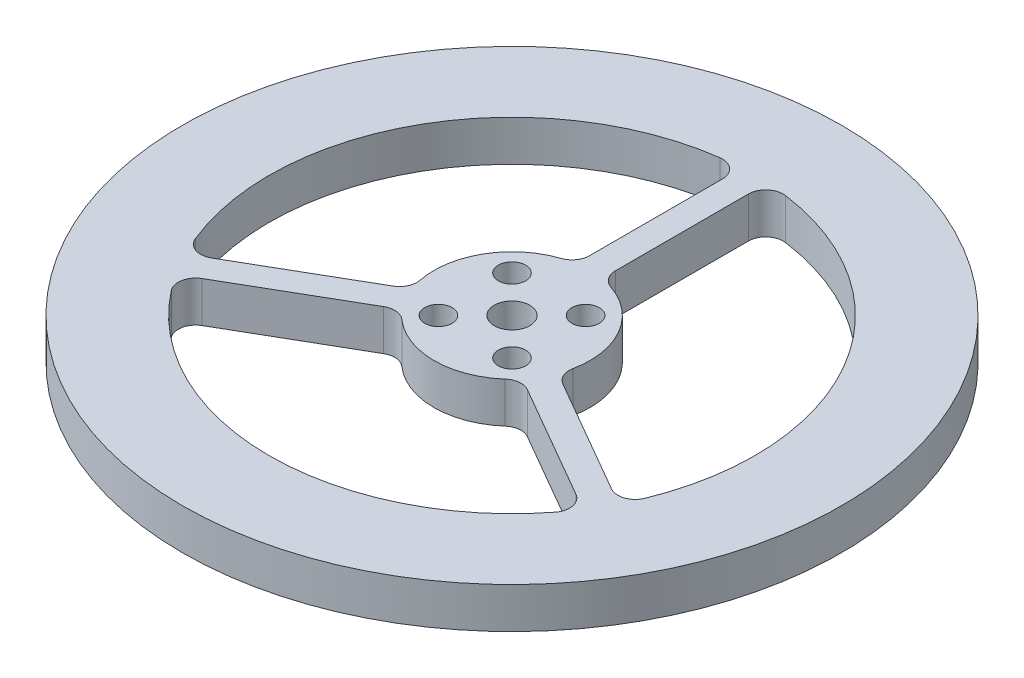
SolidWorks part; units mm, degrees
ref_plane "Front Plane" through (0, 0, 0) normal (0, 0, 1) x (1, 0, 0)
ref_plane "Top Plane" through (0, 0, 0) normal (0, 1, 0) x (1, 0, 0)
ref_plane "Right Plane" through (0, 0, 0) normal (1, 0, 0) x (0, 0, -1)
sketch "Sketch1" plane through (0, 0, 0) normal (0, 1, 0) x (1, 0, 0)
  circle A40 centre (0, 0) radius 38 construction
  circle A41 centre (0, 0) radius 28 construction
  circle A44 centre (0, 0) radius 28
  circle A45 centre (0, 0) radius 38
  dimension "D2" = 76
  dimension "D3" = 56
  dimension "D15" = 76
  dimension "D16" = 56
extrude "Boss-Extrude1" add sketch "Sketch1" along normal blind 4.7
sketch "Sketch2" plane through (0, 0, 0) normal (0, 1, 0) x (1, 0, 0)
  line L6 (-4.2426, 4.2426) -> (4.2426, -4.2426) construction
  line L7 (-4.2426, -4.2426) -> (4.2426, 4.2426) construction
  circle A7 centre (0, 0) radius 2.05
  circle A20 centre (-4.2426, 4.2426) radius 1.575
  circle A21 centre (-4.2426, -4.2426) radius 1.575
  circle A22 centre (4.2426, -4.2426) radius 1.575
  circle A23 centre (4.2426, 4.2426) radius 1.575
  circle A36 centre (-4.2426, -4.2426) radius 2.95 construction
  circle A37 centre (-4.2426, 4.2426) radius 2.95 construction
  circle A38 centre (4.2426, -4.2426) radius 2.95 construction
  circle A39 centre (4.2426, 4.2426) radius 2.95 construction
  circle A42 centre (0, 0) radius 9
  point P44 (0, 0)
  point P45 (0, 0)
  point P55 (0, 0)
  dimension "D2" = 4.1
  dimension "D3" = 18
  dimension "D4" = 3.15
  dimension "D5" = 12
  dimension "D13" = 5.9
extrude "Boss-Extrude2" add sketch "Sketch2" along normal up to surface (4.7 mm away) separate body up to face at (0, 4.7, 38)
sketch "Sketch3" plane through (0, 0, 0) normal (0, 1, 0) x (1, 0, 0)
  line L0 (0, 0) -> (0, 33) construction
  line L1 (-1.5, 29) -> (-1.5, 8.8741)
  line L2 (1.5, 29) -> (1.5, 8.8741)
  line L3 (-1.5, 15) -> (1.5, 15) construction
  line L4 (-1.5, 8.8741) -> (1.5, 8.8741)
  line L5 (-1.5, 29) -> (1.5, 29)
  line L6 (25.8647, -13.201) -> (24.3647, -15.799)
  line L7 (24.3647, -15.799) -> (6.9352, -5.7361)
  line L8 (8.4352, -3.138) -> (6.9352, -5.7361)
  line L9 (25.8647, -13.201) -> (8.4352, -3.138)
  line L10 (13.7404, -6.201) -> (12.2404, -8.799) construction
  line L11 (-24.3647, -15.799) -> (-25.8647, -13.201)
  line L12 (-25.8647, -13.201) -> (-8.4352, -3.138)
  line L13 (-6.9352, -5.7361) -> (-8.4352, -3.138)
  line L14 (-24.3647, -15.799) -> (-6.9352, -5.7361)
  line L15 (-12.2404, -8.799) -> (-13.7404, -6.201) construction
  circle A0 centre (0, 0) radius 9 construction
  point P9 (0, 15)
  point P10 (2, 15)
  point P11 (1.5917, 8.8581)
  point P25 (0, 0)
  point P27 (2, 15)
  point P28 (0, 0)
  point P29 (1, 28)
  dimension "D1" = 3
  dimension "D2" = 3
extrude "Boss-Extrude3" add sketch "Sketch3" along normal up to surface (4.7 mm away) up to face at (0, 4.7, 38)
fillet "Fillet1" radius 2 6 edges at (24.9639, 2.35, 12.6809) (23.4639, 2.35, 15.2789) (1.5, 2.35, -27.9598) (-1.5, 2.35, -27.9598) (-24.9639, 2.35, 12.6809) (-23.4639, 2.35, 15.2789)
fillet "Fillet2" radius 2 6 edges at (1.5, 2.35, -8.8741) (-1.5, 2.35, -8.8741) (-8.4352, 2.35, 3.138) (8.4352, 2.35, 3.138) (6.9352, 2.35, 5.7361) (-6.9352, 2.35, 5.7361)
